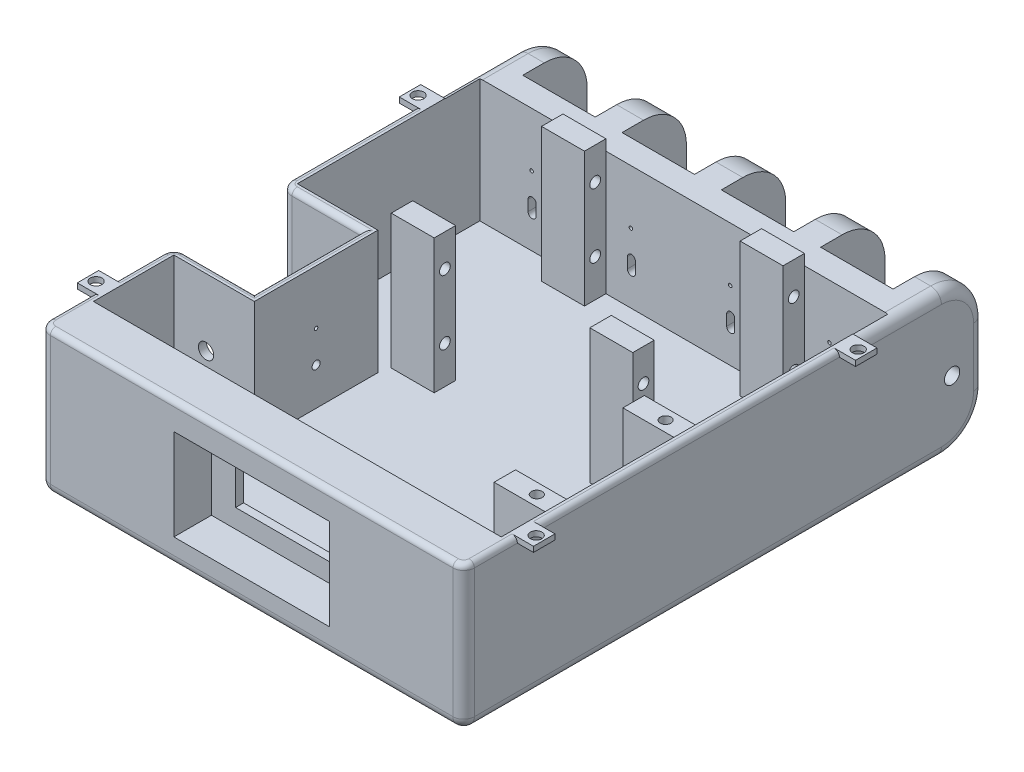
SolidWorks part; units mm, degrees
ref_plane "Front Plane" through (0, 0, 0) normal (0, 0, 1) x (1, 0, 0)
ref_plane "Top Plane" through (0, 0, 0) normal (0, 1, 0) x (1, 0, 0)
ref_plane "Right Plane" through (0, 0, 0) normal (1, 0, 0) x (0, 0, -1)
sketch "Sketch2" plane through (0, 0, 0) normal (0, 1, 0) x (1, 0, 0)
  line L0 (0, 0) -> (79, 0)
  line L1 (79, 0) -> (79, 90)
  line L2 (79, 90) -> (74, 90)
  line L3 (74, 90) -> (74, 78)
  line L4 (74, 78) -> (60.5, 78)
  line L5 (60.5, 78) -> (60.5, 90)
  line L6 (60.5, 90) -> (55.5, 90)
  line L7 (55.5, 90) -> (55.5, 78)
  line L8 (55.5, 78) -> (42, 78)
  line L9 (42, 78) -> (42, 90)
  line L10 (42, 90) -> (37, 90)
  line L11 (37, 90) -> (37, 78)
  line L12 (37, 78) -> (23.5, 78)
  line L13 (23.5, 78) -> (23.5, 90)
  line L14 (23.5, 90) -> (18.5, 90)
  line L15 (18.5, 90) -> (18.5, 78)
  line L16 (18.5, 78) -> (5, 78)
  line L17 (5, 78) -> (5, 90)
  line L18 (5, 90) -> (0, 90)
  line L19 (0, 90) -> (0, 38)
  line L20 (0, 38) -> (15, 38)
  line L21 (15, 38) -> (15, 18)
  line L22 (15, 18) -> (0, 18)
  line L23 (0, 18) -> (0, 0)
  dimension "D1" = 5
  dimension "D2" = 5
  dimension "D3" = 5
  dimension "D4" = 79
  dimension "D5" = 5
  dimension "D6" = 5
  dimension "D7" = 13.5
  dimension "D8" = 13.5
  dimension "D9" = 13.5
  dimension "D10" = 90
  dimension "D11" = 90
  dimension "D12" = 12
  dimension "D13" = 12
  dimension "D14" = 12
  dimension "D15" = 12
  dimension "D16" = 12
  dimension "D17" = 12
  dimension "D18" = 12
  dimension "D19" = 40
  dimension "D20" = 20
  dimension "D21" = 15
extrude "Boss-Extrude1" add sketch "Sketch2" along normal blind 27
sketch "Sketch3" plane through (74, 0, 0) normal (-1, 0, 0) x (0, 0, 1)
  line L0 (-90, 27) -> (-90, 0) construction
  line L1 (-90, 0) -> (-78, 0) construction
  circle A0 centre (-84, 12.5) radius 1.425
  dimension "D3" = 2.85
  dimension "D1" = 6
  dimension "D2" = 12.5
sketch "Sketch4" plane through (0, 27, 0) normal (0, 1, 0) x (1, 0, 0)
  line L0 (0, 38) -> (15, 38)
  line L1 (15, 38) -> (15, 18)
  line L2 (15, 18) -> (0, 18)
  line L3 (0, 18) -> (0, 0)
  line L4 (0, 0) -> (79, 0)
  line L5 (79, 0) -> (79, 75)
  line L6 (79, 0) -> (79, 90) construction
  line L7 (79, 75) -> (0, 75)
  line L8 (0, 90) -> (0, 38) construction
  line L9 (0, 75) -> (0, 38)
  line L10 (1.5, 73.5) -> (1.5, 39.5)
  line L11 (1.5, 39.5) -> (16.5, 39.5)
  line L12 (16.5, 39.5) -> (16.5, 16.5)
  line L13 (16.5, 16.5) -> (1.5, 16.5)
  line L14 (1.5, 16.5) -> (1.5, 1.5)
  line L15 (1.5, 1.5) -> (77.5, 1.5)
  line L16 (77.5, 1.5) -> (77.5, 73.5)
  line L17 (77.5, 73.5) -> (1.5, 73.5)
  dimension "D1" = 75
  dimension "D2" = 1.5
extrude "Cut-Extrude2" cut sketch "Sketch4" against normal blind 23 contours L10 L11 L12 L13 L14 L15 L16 L17
sketch "Sketch9" plane through (0, 0, -38) normal (0, 0, 1) x (1, 0, 0)
  line L0 (0, 27) -> (15, 27) construction
  line L1 (0, 27) -> (0, 0) construction
  circle A0 centre (7.5, 14.5) radius 1.425
  dimension "D3" = 2.85
  dimension "D1" = 12.5
  dimension "D2" = 7.5
fillet "Fillet1" radius 8 10 edges at (2.5, 0, -90) (21, 0, -90) (39.5, 0, -90) (58, 0, -90) (76.5, 0, -90) (76.5, 27, -90) (58, 27, -90) (39.5, 27, -90) (21, 27, -90) (2.5, 27, -90)
sketch "Sketch10" plane through (0, 0, -73.5) normal (0, 0, 1) x (1, 0, 0)
  line L0 (77.5, 27) -> (1.5, 27) construction
  line L1 (1.5, 4) -> (1.5, 27) construction
  line L2 (10.5, 10) -> (10.5, 11.9796)
  line L3 (12, 10) -> (12, 11.9796)
  arc A0 (10.5, 10) -> (12, 10) centre (11.25, 10) ccw
  arc A1 (12, 11.9796) -> (10.5, 11.9796) centre (11.25, 11.9796) ccw
  dimension "D1" = 1.5
  dimension "D2" = 17
  dimension "D3" = 9.75
extrude "Cut-Extrude4" cut sketch "Sketch10" against normal blind 10 contours A0 L3 A1 L2
pattern_linear "LPattern2" count 2 spacing 2 along (0, 0, 1) count 4 spacing 18.5 along (1, 0, 0) of "Cut-Extrude4"
sketch "Sketch11" plane through (16.5, 0, 0) normal (1, 0, 0) x (0, 0, -1)
  line L1 (16.5, 4) -> (16.5, 27) construction
  line L2 (39.5, 27) -> (16.5, 27) construction
  circle A0 centre (28, 11) radius 0.75
  dimension "D3" = 1.5
  dimension "D1" = 11.5
  dimension "D2" = 16
extrude "Cut-Extrude5" cut sketch "Sketch11" against normal blind 2
sketch "Sketch13" plane through (79, 0, 0) normal (1, 0, 0) x (0, 0, -1)
  line L0 (0, 27) -> (82, 27) construction
  line L1 (3, 27) -> (7, 27)
  line L2 (3, 27) -> (3, 26)
  line L3 (3, 26) -> (7, 26)
  line L4 (7, 27) -> (7, 26)
  line L5 (0, 27) -> (0, 0) construction
  dimension "D1" = 1
  dimension "D2" = 4
  dimension "D3" = 3
extrude "Boss-Extrude4" add sketch "Sketch13" along normal blind 3
sketch "Sketch14" plane through (0, 26, 0) normal (0, -1, 0) x (-1, 0, 0)
  line L0 (-82, 3) -> (-82, 7) construction
  line L1 (-82, 7) -> (-79, 7) construction
  circle A0 centre (-80.5, 5) radius 1.0783
  dimension "D1" = 1.5
  dimension "D2" = 2
extrude "Cut-Extrude6" cut sketch "Sketch14" against normal through all contours A0
pattern_linear "LPattern3" count 2 spacing 60 along (0, 0, -1) count 2 spacing 82 along (-1, 0, 0) of "Boss-Extrude4"
pattern_linear "LPattern4" count 2 spacing 60 along (0, 0, -1) count 2 spacing 82 along (-1, 0, 0) of "Cut-Extrude6"
extrude "Cut-Extrude7" cut sketch "Sketch3" along normal through all and the other way blind 19
extrude "Cut-Extrude8" cut sketch "Sketch9" along normal blind 25 and the other way blind 5
sketch "Sketch15" plane through (0, 0, -73.5) normal (0, 0, 1) x (1, 0, 0)
  line L0 (1.5, 4) -> (1.5, 27) construction
  line L1 (77.5, 4) -> (1.5, 4) construction
  circle A0 centre (11.15, 16.9) radius 0.325
  dimension "D2" = 0.65
  dimension "D1" = 9.65
  dimension "D3" = 12.9
extrude "Cut-Extrude9" cut sketch "Sketch15" against normal through all
pattern_linear "LPattern5" count 4 spacing 18.5 along (1, 0, 0) of "Cut-Extrude9"
sketch "Sketch16" plane through (16.5, 0, 0) normal (1, 0, 0) x (0, 0, -1)
  line L0 (16.5, 4) -> (16.5, 27) construction
  line L1 (39.5, 4) -> (16.5, 4) construction
  circle A0 centre (28, 16.9) radius 0.325
  dimension "D2" = 0.65
  dimension "D1" = 11.5
  dimension "D3" = 12.9
extrude "Cut-Extrude10" cut sketch "Sketch16" against normal through all
sketch "Sketch20" plane through (0, 0, 0) normal (0, 0, 1) x (1, 0, 0)
  line L1 (0, 27) -> (79, 27)
  line L2 (0, 27) -> (0, 0)
  line L3 (0, 0) -> (79, 0)
  line L4 (79, 27) -> (79, 0)
extrude "Boss-Extrude7" add sketch "Sketch20" along normal blind 7
sketch "Sketch21" plane through (0, 0, 7) normal (0, 0, 1) x (1, 0, 0)
  line L1 (25, 22) -> (54, 22)
  line L2 (25, 22) -> (25, 5)
  line L3 (25, 5) -> (54, 5)
  line L4 (54, 22) -> (54, 5)
  line L5 (0, 27) -> (0, 0) construction
  line L7 (79, 27) -> (0, 27) construction
  dimension "D1" = 17
  dimension "D2" = 29
  dimension "D3" = 25
  dimension "D4" = 5
extrude "Cut-Extrude13" cut sketch "Sketch21" against normal blind 7
sketch "Sketch24" plane through (0, 0, 0) normal (0, 0, 1) x (1, 0, 0)
  line L0 (0, 0) -> (79, 0) construction
  line L1 (29.5, 18.5) -> (49.5, 18.5)
  line L2 (29.5, 18.5) -> (29.5, 8.5)
  line L3 (29.5, 8.5) -> (49.5, 8.5)
  line L4 (49.5, 18.5) -> (49.5, 8.5)
  line L5 (79, 0) -> (79, 27) construction
  dimension "D1" = 10
  dimension "D2" = 20
  dimension "D3" = 8.5
  dimension "D4" = 29.5
extrude "Cut-Extrude14" cut sketch "Sketch24" against normal up to next
fillet "Fillet7" radius 2 18 edges at (0, 27, -74.5) (79, 27, -74.5) (79, 2.3431, -87.6569) (79, 13.5, -90) (79, 24.6569, -87.6569) (79, 0, -37.5) (79, 13.5, 7) (39.5, 0, 7) (0, 13.5, 7) (0, 13.5, -18) (0, 0, -5.5) (15, 0, -28) (7.5, 0, -38) (0, 13.5, -38) (0, 0, -60) (0, 2.3431, -87.6569) (0, 13.5, -90) (0, 24.6569, -87.6569)
fillet "Fillet8" radius 1 19 edges at (79, 27, -35) (79, 26.5, -3) (79, 26.5, -7) (0, 27, -51.5) (0, 27, 1) (0, 26.5, -3) (0, 26.5, -7) (79, 26.5, -63) (0, 26.5, -63) (79, 27, 1) (8.5, 27, -38) (0, 27, -11.5) (39.5, 27, 7) (0.5858, 27, -38.5858) (0.5858, 27, -17.4142) (0.5858, 27, 6.4142) (78.4142, 27, 6.4142) (15, 27, -28) (8.5, 27, -18)
sketch "Sketch28" plane through (0, 4, 0) normal (0, 1, 0) x (1, 0, 0)
  line L0 (77.5, 73.5) -> (1.5, 73.5) construction
  line L1 (17, 73.5) -> (25, 73.5)
  line L2 (17, 73.5) -> (17, 69.5)
  line L3 (17, 69.5) -> (25, 69.5)
  line L4 (25, 73.5) -> (25, 69.5)
  line L5 (1.5, 73.5) -> (1.5, 67) construction
  line L7 (17, 45.5) -> (25, 45.5)
  line L8 (17, 45.5) -> (17, 41.5)
  line L9 (17, 41.5) -> (25, 41.5)
  line L10 (25, 45.5) -> (25, 41.5)
  dimension "D1" = 4
  dimension "D2" = 8
  dimension "D3" = 15.5
  dimension "D4" = 4
  dimension "D5" = 24
extrude "Boss-Extrude8" add sketch "Sketch28" along normal blind 25
sketch "Sketch30" plane through (25, 0, 0) normal (1, 0, 0) x (0, 0, -1)
  line L0 (41.5, 29) -> (41.5, 4) construction
  line L1 (41.5, 4) -> (45.5, 4) construction
  line L2 (69.5, 29) -> (69.5, 4) construction
  line L3 (69.5, 4) -> (73.5, 4) construction
  circle A0 centre (43.5, 11) radius 1
  circle A1 centre (43.5, 23) radius 1
  circle A2 centre (71.5, 11) radius 1
  circle A3 centre (71.5, 23) radius 1
  dimension "D1" = 2
  dimension "D4" = 2
  dimension "D6" = 2
  dimension "D9" = 2
  dimension "D2" = 2
  dimension "D3" = 7
  dimension "D5" = 12
  dimension "D7" = 2
  dimension "D8" = 7
extrude "Cut-Extrude15" cut sketch "Sketch30" against normal blind 8
pattern_linear "LPattern6" count 4 spacing 37 along (1, 0, 0) of "Boss-Extrude8"
pattern_linear "LPattern7" count 2 spacing 37 along (1, 0, 0) of "Cut-Extrude15"
sketch "Sketch32" plane through (0, 4, 0) normal (0, 1, 0) x (1, 0, 0)
  line L0 (77.5, 1.5) -> (77.5, 73.5) construction
  line L1 (77.5, 40.6591) -> (65, 40.6591)
  line L2 (77.5, 40.6591) -> (77.5, 36.6591)
  line L3 (77.5, 36.6591) -> (65, 36.6591)
  line L4 (65, 40.6591) -> (65, 36.6591)
  dimension "D1" = 4
  dimension "D2" = 12.5
extrude "Boss-Extrude9" add sketch "Sketch32" along normal blind 20
pattern_linear "LPattern8" count 2 spacing 24 along (0, 0, 1) of "Boss-Extrude9"
sketch "Sketch33" plane through (0, 24, 0) normal (0, 1, 0) x (1, 0, 0)
  line L0 (77.5, 40.6591) -> (65, 40.6591) construction
  circle A0 centre (70.9602, 38.6591) radius 1
  dimension "D1" = 2
  dimension "D2" = 2
extrude "Cut-Extrude16" cut sketch "Sketch33" against normal blind 5
pattern_linear "LPattern9" count 2 spacing 24 along (0, 0, 1) of "Cut-Extrude16"
